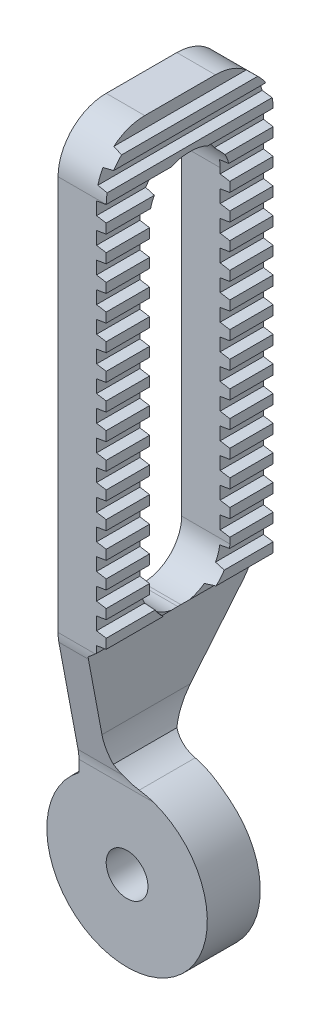
SolidWorks part; units mm, degrees
ref_plane "Front Plane" through (0, 0, 0) normal (0, 0, 1) x (1, 0, 0)
ref_plane "Top Plane" through (0, 0, 0) normal (0, 1, 0) x (1, 0, 0)
ref_plane "Right Plane" through (0, 0, 0) normal (1, 0, 0) x (0, 0, -1)
sketch "Sketch1" plane through (0, 0, 0) normal (0, 0, 1) x (1, 0, 0)
  circle A0 centre (0, 0) radius 2.5
  dimension "D1" = 5
extrude "Extrude1" add sketch "Sketch1" along normal blind 1.65
sketch "Sketch2" plane through (0, 0, 1.65) normal (0, 0, 1) x (1, 0, 0)
  circle A0 centre (0, 0) radius 0.65
  dimension "D1" = 1.3
extrude "Extrude2" cut sketch "Sketch2" against normal through all
sketch "Sketch3" plane through (0, 0, 0) normal (0, 1, 0) x (1, 0, 0)
  line L0 (-2.5, -1.65) -> (2.5, -1.65) construction
  line L1 (-1.5, 2.9) -> (0, 2.9)
  line L2 (-1.5, 2.9) -> (-1.5, -2.3)
  line L3 (-1.5, -2.3) -> (0, -2.3)
  line L4 (0, 2.9) -> (0, -2.3)
  line L6 (0.65, -1.65) -> (0.65, 0) construction
  dimension "D1" = 0.65
  dimension "D2" = 5.2
  dimension "D3" = 1.5
  dimension "D4" = 0.65
extrude "Extrude4" add sketch "Sketch3" along normal blind 19.9
sketch "Sketch4" plane through (0, 0, 0) normal (1, 0, 0) x (0, 0, -1)
  line L0 (0, 0) -> (0, 2.5)
  line L3 (0, -2.5) -> (0, 2.5) construction
  line L4 (0, 2.5) -> (2.9, 6)
  line L5 (2.9, 19.9) -> (2.9, 0) construction
  line L6 (2.9, 6) -> (2.9, 1.4932)
  line L7 (2.9, 1.4932) -> (2.9, 0)
  line L8 (-2.3, 0) -> (2.9, 0) construction
  line L9 (2.9, 0) -> (0, 0)
  dimension "D1" = 4.5068
  dimension "D2" = 3.5
extrude "Extrude5" cut sketch "Sketch4" against normal through all
fillet "Fillet1" radius 1.5 2 edges at (-0.75, 19.9, 2.3) (-0.75, 19.9, -2.9)
sketch "Sketch5" plane through (0, 0, 0) normal (1, 0, 0) x (0, 0, -1)
  line L0 (-2.3, 18.4) -> (-2.3, 0) construction
  line L1 (0.25, 18.52) -> (0.35, 18.52)
  line L2 (-0.95, 17.32) -> (-0.95, 7.32)
  line L3 (0.25, 6.12) -> (0.35, 6.12)
  line L4 (1.55, 17.32) -> (1.55, 7.32)
  line L7 (-0.8, 19.9) -> (1.4, 19.9) construction
  arc A0 (0.35, 18.52) -> (1.55, 17.32) centre (0.35, 17.32) cw
  arc A1 (0.25, 18.52) -> (-0.95, 17.32) centre (0.25, 17.32) ccw
  arc A2 (0.25, 6.12) -> (-0.95, 7.32) centre (0.25, 7.32) cw
  arc A3 (1.55, 7.32) -> (0.35, 6.12) centre (0.35, 7.32) cw
  point P10 (1.55, 18.52)
  point P13 (-0.95, 18.52)
  point P16 (-0.95, 6.12)
  dimension "D5" = 1.2
  dimension "D6" = 1.2
  dimension "D1" = 12.4
  dimension "D2" = 2.5
  dimension "D3" = 1.35
  dimension "D4" = 1.38
extrude "Extrude6" cut sketch "Sketch5" against normal through all
sketch "Sketch6" plane through (0, 0, 0) normal (1, 0, 0) x (0, 0, -1)
  line L0 (-1.65, 0) -> (-3.658, 0)
  line L1 (-3.658, 0) -> (-3.658, 5.9662)
  line L3 (-3.658, 5.9662) -> (-2.3, 5.9662)
  line L4 (-2.3, 18.4) -> (-2.3, 0) construction
  line L5 (-2.3, 5.9662) -> (-1.65, 2.5)
  line L6 (-1.65, 2.5) -> (-1.65, 0)
extrude "Extrude7" cut sketch "Sketch6" against normal through all
sketch "Sketch7" plane through (0, 0, 0) normal (0, 0, -1) x (-1, 0, 0)
  circle A0 centre (0, 0) radius 0.65
extrude "Extrude8" cut sketch "Sketch7" against normal through all
sketch "Sketch9" plane through (0, 0, 2.3) normal (0, 0, 1) x (1, 0, 0)
  line L0 (0, 20) -> (-0.3, 19.95)
  line L1 (0, 18.7) -> (0, 19.2)
  line L2 (0, 18.4) -> (0, 19.9) construction
  line L3 (-0.3, 19.95) -> (-0.3, 19.55)
  line L4 (-0.3, 19.55) -> (0, 19.5)
  line L5 (0, 19.5) -> (0, 20)
  line L6 (0, 19.2) -> (-0.3, 19.15)
  line L7 (-0.3, 19.15) -> (-0.3, 18.75)
  line L8 (-0.3, 18.75) -> (0, 18.7)
  line L9 (0, 17.9) -> (0, 18.4)
  line L10 (0, 18.4) -> (-0.3, 18.35)
  line L11 (-0.3, 18.35) -> (-0.3, 17.95)
  line L12 (-0.3, 17.95) -> (0, 17.9)
  line L13 (0, 17.1) -> (0, 17.6)
  line L14 (0, 17.6) -> (-0.3, 17.55)
  line L15 (-0.3, 17.55) -> (-0.3, 17.15)
  line L16 (-0.3, 17.15) -> (0, 17.1)
  line L17 (0, 16.3) -> (0, 16.8)
  line L18 (0, 16.8) -> (-0.3, 16.75)
  line L19 (-0.3, 16.75) -> (-0.3, 16.35)
  line L20 (-0.3, 16.35) -> (0, 16.3)
  line L21 (0, 15.5) -> (0, 16)
  line L22 (0, 16) -> (-0.3, 15.95)
  line L23 (-0.3, 15.95) -> (-0.3, 15.55)
  line L24 (-0.3, 15.55) -> (0, 15.5)
  line L25 (0, 14.7) -> (0, 15.2)
  line L26 (0, 15.2) -> (-0.3, 15.15)
  line L27 (-0.3, 15.15) -> (-0.3, 14.75)
  line L28 (-0.3, 14.75) -> (0, 14.7)
  line L29 (0, 13.9) -> (0, 14.4)
  line L30 (0, 14.4) -> (-0.3, 14.35)
  line L31 (-0.3, 14.35) -> (-0.3, 13.95)
  line L32 (-0.3, 13.95) -> (0, 13.9)
  line L33 (0, 13.1) -> (0, 13.6)
  line L34 (0, 13.6) -> (-0.3, 13.55)
  line L35 (-0.3, 13.55) -> (-0.3, 13.15)
  line L36 (-0.3, 13.15) -> (0, 13.1)
  line L37 (0, 12.3) -> (0, 12.8)
  line L38 (0, 12.8) -> (-0.3, 12.75)
  line L39 (-0.3, 12.75) -> (-0.3, 12.35)
  line L40 (-0.3, 12.35) -> (0, 12.3)
  line L41 (0, 11.5) -> (0, 12)
  line L42 (0, 12) -> (-0.3, 11.95)
  line L43 (-0.3, 11.95) -> (-0.3, 11.55)
  line L44 (-0.3, 11.55) -> (0, 11.5)
  line L45 (0, 10.7) -> (0, 11.2)
  line L46 (0, 11.2) -> (-0.3, 11.15)
  line L47 (-0.3, 11.15) -> (-0.3, 10.75)
  line L48 (-0.3, 10.75) -> (0, 10.7)
  line L49 (0, 9.9) -> (0, 10.4)
  line L50 (0, 10.4) -> (-0.3, 10.35)
  line L51 (-0.3, 10.35) -> (-0.3, 9.95)
  line L52 (-0.3, 9.95) -> (0, 9.9)
  line L53 (0, 9.1) -> (0, 9.6)
  line L54 (0, 9.6) -> (-0.3, 9.55)
  line L55 (-0.3, 9.55) -> (-0.3, 9.15)
  line L56 (-0.3, 9.15) -> (0, 9.1)
  line L57 (0, 8.3) -> (0, 8.8)
  line L58 (0, 8.8) -> (-0.3, 8.75)
  line L59 (-0.3, 8.75) -> (-0.3, 8.35)
  line L60 (-0.3, 8.35) -> (0, 8.3)
  line L61 (0, 7.5) -> (0, 8)
  line L62 (0, 8) -> (-0.3, 7.95)
  line L63 (-0.3, 7.95) -> (-0.3, 7.55)
  line L64 (-0.3, 7.55) -> (0, 7.5)
  line L65 (0, 6.7) -> (0, 7.2)
  line L66 (0, 7.2) -> (-0.3, 7.15)
  line L67 (-0.3, 7.15) -> (-0.3, 6.75)
  line L68 (-0.3, 6.75) -> (0, 6.7)
  line L69 (0, 5.9) -> (0, 6.4)
  line L70 (0, 6.4) -> (-0.3, 6.35)
  line L71 (-0.3, 6.35) -> (-0.3, 5.95)
  line L72 (-0.3, 5.95) -> (0, 5.9)
  dimension "D1" = 0.5
  dimension "D2" = 0.4
  dimension "D3" = 0.05
  dimension "D4" = 0.05
  dimension "D5" = 0.3
extrude "Extrude10" cut sketch "Sketch9" against normal through all
sketch "Sketch11" plane through (0, 0, 2.3) normal (0, 0, 1) x (1, 0, 0)
  line L0 (0, 6.4) -> (-0.5786, 5.9)
  line L1 (0, 2.5) -> (0, 5.9) construction
  line L2 (-0.5786, 5.9) -> (-0.5786, 3)
  line L3 (-0.5786, 3) -> (0, 2.5)
  line L4 (0, 2.5) -> (0, 6.4)
  dimension "D1" = 0.5
  dimension "D2" = 0.5
extrude "Extrude11" cut sketch "Sketch11" against normal through all
fillet "Fillet2" radius 1.5 3 edges at (-0.75, 2.5, 0) (0, 2.5, 0.825) (-0.75, 2.5, 1.65)
fillet "Fillet3" radius 1.5 3 edges at (-0.5786, 3, 0.6647) (-0.9814, 6, -2.9) (-1.001, 5.9662, 2.3)
ref_point "Point1"
